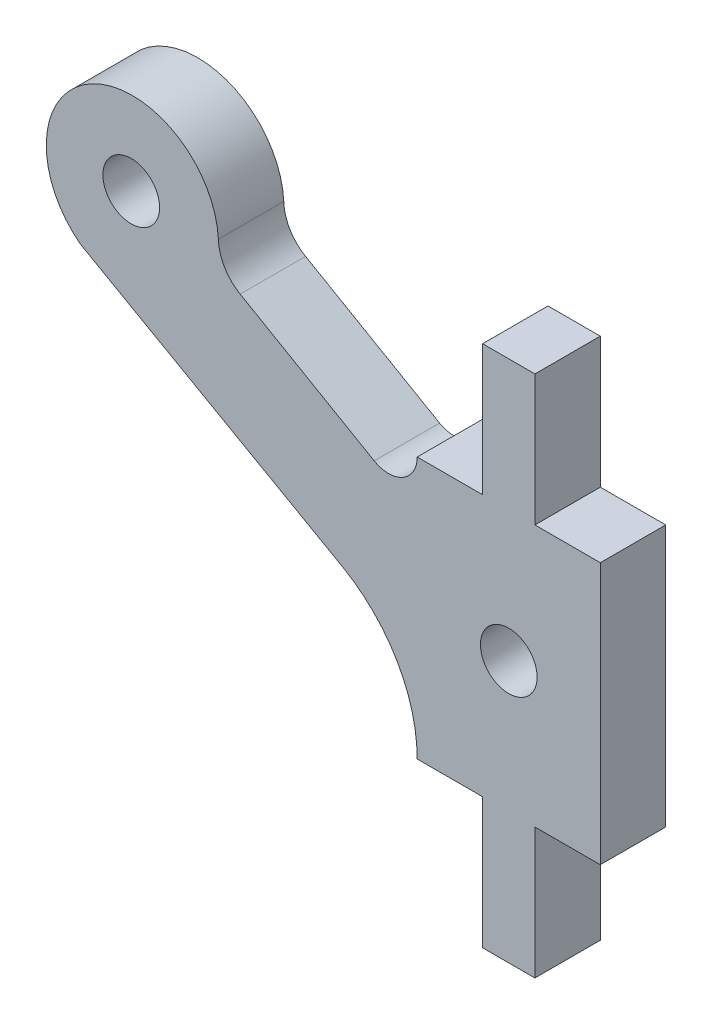
SolidWorks part; units mm, degrees
ref_plane "Front Plane" through (0, 0, 0) normal (0, 0, 1) x (1, 0, 0)
ref_plane "Top Plane" through (0, 0, 0) normal (0, 1, 0) x (1, 0, 0)
ref_plane "Right Plane" through (0, 0, 0) normal (1, 0, 0) x (0, 0, -1)
sketch "Model" plane through (0, 0, 0) normal (0, 0, 1) x (1, 0, 0)
  line L0 (74.2314, 47.6131) -> (74.2314, 35.6131)
  line L1 (71.2314, 35.6131) -> (74.2314, 35.6131)
  line L2 (71.2314, 29.6131) -> (71.2314, 35.6131)
  line L3 (68.8314, 29.6131) -> (71.2314, 29.6131)
  line L4 (68.8314, 35.6129) -> (68.8314, 29.6131)
  line L5 (65.8314, 35.6129) -> (68.8314, 35.6129)
  line L6 (50.3936, 48.3334) -> (62.4144, 41.5323)
  line L7 (63.8572, 46.4729) -> (57.7102, 50.0224)
  line L8 (68.8314, 47.613) -> (65.8314, 47.613)
  line L9 (68.8314, 53.6131) -> (68.8314, 47.613)
  line L10 (71.2314, 53.6131) -> (68.8314, 53.6131)
  line L11 (71.2314, 47.6131) -> (71.2314, 53.6131)
  line L12 (74.2314, 47.6131) -> (71.2314, 47.6131)
  circle A0 centre (70.0318, 41.6127) radius 1.3
  circle A1 centre (52.712, 51.614) radius 1.3
  arc A2 (65.8314, 35.6129) -> (62.4144, 41.5323) centre (58.9968, 35.6136) ccw
  arc A3 (56.7109, 51.7077) -> (50.3936, 48.3334) centre (52.7658, 51.4928) ccw
  arc A4 (56.7109, 51.7077) -> (57.7102, 50.0224) centre (58.7104, 51.7544) ccw
  arc A5 (63.8572, 46.4729) -> (65.8314, 47.613) centre (64.5148, 47.6135) ccw
  dimension "D1" = 12
  dimension "D2" = 2.4
  dimension "D3" = 6
  dimension "D4" = 6
  dimension "D5" = 8.4
  dimension "D6" = 8.4
extrude "Boss-Extrude1" add sketch "Model" along normal blind 3 contours A5 L7 A4 A3 L6 A2 L5 L4 L3 L2 L1 L0 L12 L11 L10 L9 L8 A1 A0 region at (64.1192, 44.4753, 0)
